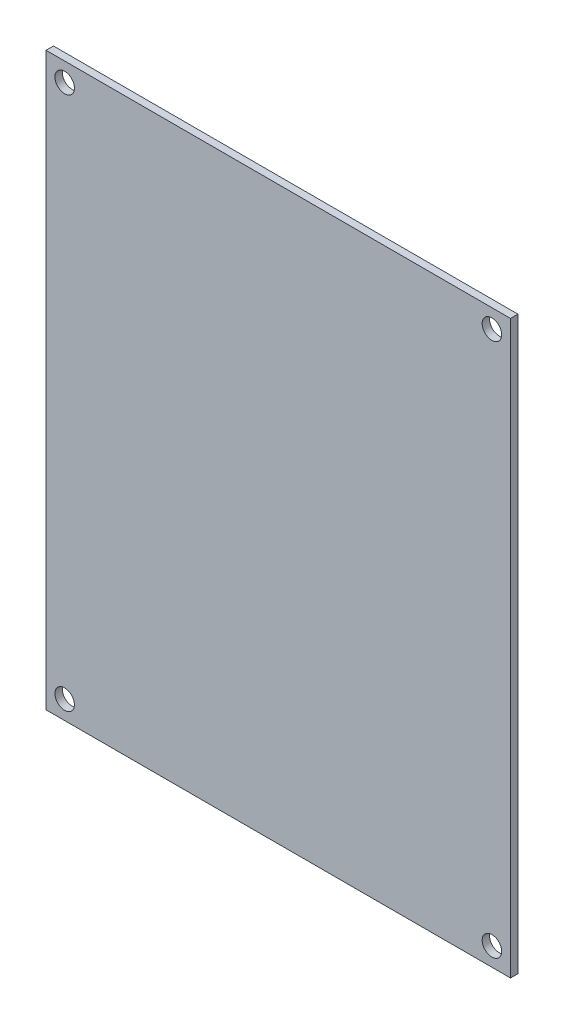
SolidWorks part; units mm, degrees
material "Custom Plastic"
ref_plane "Front Plane" through (0, 0, 0) normal (0, 0, 1) x (1, 0, 0)
ref_plane "Top Plane" through (0, 0, 0) normal (0, 1, 0) x (1, 0, 0)
ref_plane "Right Plane" through (0, 0, 0) normal (1, 0, 0) x (0, 0, -1)
sketch "Model" plane through (0, 0, 0) normal (0, 0, 1) x (1, 0, 0)
  line L0 (104.1673, 32.1811) -> (4.1672, 32.1811)
  line L1 (104.1673, 155.1806) -> (104.1673, 32.1811)
  line L2 (4.1672, 155.1806) -> (104.1673, 155.1806)
  line L3 (4.1672, 32.1811) -> (4.1672, 155.1806)
  line L4 (44.9158, 146.4259) -> (47.4224, 146.4259)
  line L5 (47.4224, 146.4259) -> (47.4224, 148.9326)
  line L6 (47.4224, 148.9326) -> (44.9158, 148.9326)
  line L7 (44.9158, 148.9326) -> (44.9158, 146.4259)
  line L8 (77.4127, 147.4278) -> (79.9193, 147.4278)
  line L9 (79.9193, 147.4278) -> (79.9193, 149.9344)
  line L10 (79.9193, 149.9344) -> (77.4127, 149.9344)
  line L11 (77.4127, 149.9344) -> (77.4127, 147.4278)
  line L12 (6.3266, 141.9721) -> (8.3592, 141.9721)
  line L13 (8.3592, 141.9721) -> (8.3592, 144.0047)
  line L14 (8.3592, 144.0047) -> (6.3266, 144.0047)
  line L15 (6.3266, 144.0047) -> (6.3266, 141.9721)
  line L16 (6.3266, 121.6529) -> (8.3592, 121.6529)
  line L17 (8.3592, 121.6529) -> (8.3592, 123.6855)
  line L18 (8.3592, 123.6855) -> (6.3266, 123.6855)
  line L19 (6.3266, 123.6855) -> (6.3266, 121.6529)
  line L20 (6.3266, 101.3324) -> (8.3592, 101.3324)
  line L21 (8.3592, 101.3324) -> (8.3592, 103.365)
  line L22 (8.3592, 103.365) -> (6.3266, 103.365)
  line L23 (6.3266, 103.365) -> (6.3266, 101.3324)
  line L24 (6.3266, 81.0118) -> (8.3592, 81.0118)
  line L25 (8.3592, 81.0118) -> (8.3592, 83.0444)
  line L26 (8.3592, 83.0444) -> (6.3266, 83.0444)
  line L27 (6.3266, 83.0444) -> (6.3266, 81.0118)
  line L28 (6.3266, 60.6927) -> (8.3592, 60.6927)
  line L29 (8.3592, 60.6927) -> (8.3592, 62.7253)
  line L30 (8.3592, 62.7253) -> (6.3266, 62.7253)
  line L31 (6.3266, 62.7253) -> (6.3266, 60.6927)
  line L32 (85.9221, 148.4144) -> (87.9547, 148.4144)
  line L33 (87.9547, 148.4144) -> (87.9547, 150.447)
  line L34 (87.9547, 150.447) -> (85.9221, 150.447)
  line L35 (85.9221, 150.447) -> (85.9221, 148.4144)
  line L36 (6.3266, 50.5324) -> (8.3592, 50.5324)
  line L37 (8.3592, 50.5324) -> (8.3592, 52.565)
  line L38 (8.3592, 52.565) -> (6.3266, 52.565)
  line L39 (6.3266, 52.565) -> (6.3266, 50.5324)
  line L40 (6.3266, 42.9118) -> (8.3592, 42.9118)
  line L41 (8.3592, 42.9118) -> (8.3592, 44.9444)
  line L42 (8.3592, 44.9444) -> (6.3266, 44.9444)
  line L43 (6.3266, 44.9444) -> (6.3266, 42.9118)
  line L44 (52.8726, 50.0418) -> (54.3815, 50.0418)
  line L45 (54.3815, 50.0418) -> (54.3815, 51.5508)
  line L46 (54.3815, 51.5508) -> (52.8726, 51.5508)
  line L47 (52.8726, 51.5508) -> (52.8726, 50.0418)
  line L48 (58.4219, 130.1637) -> (60.4545, 130.1637)
  line L49 (60.4545, 130.1637) -> (60.4545, 132.1963)
  line L50 (60.4545, 132.1963) -> (58.4219, 132.1963)
  line L51 (58.4219, 132.1963) -> (58.4219, 130.1637)
  line L52 (97.8807, 141.1439) -> (99.9133, 141.1439)
  line L53 (99.9133, 141.1439) -> (99.9133, 143.1765)
  line L54 (99.9133, 143.1765) -> (97.8807, 143.1765)
  line L55 (97.8807, 143.1765) -> (97.8807, 141.1439)
  line L56 (48.438, 37.3046) -> (48.438, 37.0552)
  line L57 (49.9456, 37.0552) -> (49.9456, 37.3046)
  line L58 (52.8877, 37.3046) -> (52.8877, 37.0552)
  line L59 (54.3967, 37.0552) -> (54.3967, 37.3046)
  line L60 (54.3126, 34.0993) -> (54.3126, 33.8995)
  line L61 (56.7201, 33.8995) -> (56.7201, 34.0993)
  line L62 (46.1133, 34.0993) -> (46.1133, 33.8995)
  line L63 (48.5207, 33.8995) -> (48.5207, 34.0993)
  line L64 (82.9607, 49.0165) -> (84.9933, 49.0165)
  line L65 (84.9933, 49.0165) -> (84.9933, 51.0492)
  line L66 (84.9933, 51.0492) -> (82.9607, 51.0492)
  line L67 (82.9607, 51.0492) -> (82.9607, 49.0165)
  line L68 (29.8828, 70.9163) -> (31.9154, 70.9163)
  line L69 (31.9154, 70.9163) -> (31.9154, 72.9489)
  line L70 (31.9154, 72.9489) -> (29.8828, 72.9489)
  line L71 (29.8828, 72.9489) -> (29.8828, 70.9163)
  line L72 (29.8828, 68.1658) -> (31.9154, 68.1658)
  line L73 (31.9154, 68.1658) -> (31.9154, 70.1984)
  line L74 (31.9154, 70.1984) -> (29.8828, 70.1984)
  line L75 (29.8828, 70.1984) -> (29.8828, 68.1658)
  line L76 (29.8828, 108.6649) -> (31.9154, 108.6649)
  line L77 (31.9154, 108.6649) -> (31.9154, 110.6975)
  line L78 (31.9154, 110.6975) -> (29.8828, 110.6975)
  line L79 (29.8828, 110.6975) -> (29.8828, 108.6649)
  line L80 (29.8828, 111.4141) -> (31.9154, 111.4141)
  line L81 (31.9154, 111.4141) -> (31.9154, 113.4467)
  line L82 (31.9154, 113.4467) -> (29.8828, 113.4467)
  line L83 (29.8828, 113.4467) -> (29.8828, 111.4141)
  line L84 (29.8828, 91.1652) -> (31.9154, 91.1652)
  line L85 (31.9154, 91.1652) -> (31.9154, 93.1978)
  line L86 (31.9154, 93.1978) -> (29.8828, 93.1978)
  line L87 (29.8828, 93.1978) -> (29.8828, 91.1652)
  line L88 (29.8828, 88.4147) -> (31.9154, 88.4147)
  line L89 (31.9154, 88.4147) -> (31.9154, 90.4473)
  line L90 (31.9154, 90.4473) -> (29.8828, 90.4473)
  line L91 (29.8828, 90.4473) -> (29.8828, 88.4147)
  line L92 (29.8828, 128.6658) -> (31.9154, 128.6658)
  line L93 (31.9154, 128.6658) -> (31.9154, 130.6984)
  line L94 (31.9154, 130.6984) -> (29.8828, 130.6984)
  line L95 (29.8828, 130.6984) -> (29.8828, 128.6658)
  line L96 (29.8828, 131.4163) -> (31.9154, 131.4163)
  line L97 (31.9154, 131.4163) -> (31.9154, 133.4489)
  line L98 (31.9154, 133.4489) -> (29.8828, 133.4489)
  line L99 (29.8828, 133.4489) -> (29.8828, 131.4163)
  line L100 (48.1611, 135.1453) -> (50.1937, 135.1453)
  line L101 (50.1937, 135.1453) -> (50.1937, 137.1779)
  line L102 (50.1937, 137.1779) -> (48.1611, 137.1779)
  line L103 (48.1611, 137.1779) -> (48.1611, 135.1453)
  line L104 (11.4074, 121.6529) -> (13.44, 121.6529)
  line L105 (13.44, 121.6529) -> (13.44, 123.6855)
  line L106 (13.44, 123.6855) -> (11.4074, 123.6855)
  line L107 (11.4074, 123.6855) -> (11.4074, 121.6529)
  line L108 (104.1673, 32.1811) -> (4.1672, 32.1811)
  line L109 (104.1673, 155.1806) -> (104.1673, 32.1811)
  line L110 (4.1672, 155.1806) -> (104.1673, 155.1806)
  line L111 (4.1672, 32.1811) -> (4.1672, 155.1806)
  spline S0 degree 3 poles (55.1711, 147.6799) (55.1711, 149.685) (52.1643, 149.685) (52.1643, 147.6799) knots 0 0 0 0 1 1 1 1
  spline S1 degree 3 poles (52.1643, 147.6799) (52.1643, 145.6749) (55.1711, 145.6749) (55.1711, 147.6799) knots 0 0 0 0 1 1 1 1
  spline S2 degree 3 poles (75.1706, 148.6804) (75.1706, 150.6854) (72.1637, 150.6854) (72.1637, 148.6804) knots 0 0 0 0 1 1 1 1
  spline S3 degree 3 poles (72.1637, 148.6804) (72.1637, 146.6754) (75.1706, 146.6754) (75.1706, 148.6804) knots 0 0 0 0 1 1 1 1
  spline S4 degree 3 poles (8.3592, 140.448) (8.3592, 141.8026) (6.3266, 141.8026) (6.3266, 140.448) knots 0 0 0 0 1 1 1 1
  spline S5 degree 3 poles (6.3266, 140.448) (6.3266, 139.0934) (8.3592, 139.0934) (8.3592, 140.448) knots 0 0 0 0 1 1 1 1
  spline S6 degree 3 poles (8.3592, 137.9083) (8.3592, 139.2629) (6.3266, 139.2629) (6.3266, 137.9083) knots 0 0 0 0 1 1 1 1
  spline S7 degree 3 poles (6.3266, 137.9083) (6.3266, 136.5537) (8.3592, 136.5537) (8.3592, 137.9083) knots 0 0 0 0 1 1 1 1
  spline S8 degree 3 poles (8.3592, 135.3686) (8.3592, 136.7232) (6.3266, 136.7232) (6.3266, 135.3686) knots 0 0 0 0 1 1 1 1
  spline S9 degree 3 poles (6.3266, 135.3686) (6.3266, 134.0139) (8.3592, 134.0139) (8.3592, 135.3686) knots 0 0 0 0 1 1 1 1
  spline S10 degree 3 poles (8.3592, 132.8288) (8.3592, 134.1834) (6.3266, 134.1834) (6.3266, 132.8288) knots 0 0 0 0 1 1 1 1
  spline S11 degree 3 poles (6.3266, 132.8288) (6.3266, 131.4742) (8.3592, 131.4742) (8.3592, 132.8288) knots 0 0 0 0 1 1 1 1
  spline S12 degree 3 poles (8.3592, 130.2891) (8.3592, 131.6437) (6.3266, 131.6437) (6.3266, 130.2891) knots 0 0 0 0 1 1 1 1
  spline S13 degree 3 poles (6.3266, 130.2891) (6.3266, 128.9331) (8.3592, 128.9331) (8.3592, 130.2891) knots 0 0 0 0 1 1 1 1
  spline S14 degree 3 poles (8.3592, 127.748) (8.3592, 129.1026) (6.3266, 129.1026) (6.3266, 127.748) knots 0 0 0 0 1 1 1 1
  spline S15 degree 3 poles (6.3266, 127.748) (6.3266, 126.3934) (8.3592, 126.3934) (8.3592, 127.748) knots 0 0 0 0 1 1 1 1
  spline S16 degree 3 poles (8.3592, 120.1288) (8.3592, 121.4834) (6.3266, 121.4834) (6.3266, 120.1288) knots 0 0 0 0 1 1 1 1
  spline S17 degree 3 poles (6.3266, 120.1288) (6.3266, 118.7742) (8.3592, 118.7742) (8.3592, 120.1288) knots 0 0 0 0 1 1 1 1
  spline S18 degree 3 poles (8.3592, 117.5891) (8.3592, 118.9437) (6.3266, 118.9437) (6.3266, 117.5891) knots 0 0 0 0 1 1 1 1
  spline S19 degree 3 poles (6.3266, 117.5891) (6.3266, 116.2331) (8.3592, 116.2331) (8.3592, 117.5891) knots 0 0 0 0 1 1 1 1
  spline S20 degree 3 poles (8.3592, 115.048) (8.3592, 116.4026) (6.3266, 116.4026) (6.3266, 115.048) knots 0 0 0 0 1 1 1 1
  spline S21 degree 3 poles (6.3266, 115.048) (6.3266, 113.6934) (8.3592, 113.6934) (8.3592, 115.048) knots 0 0 0 0 1 1 1 1
  spline S22 degree 3 poles (8.3592, 112.5083) (8.3592, 113.8629) (6.3266, 113.8629) (6.3266, 112.5083) knots 0 0 0 0 1 1 1 1
  spline S23 degree 3 poles (6.3266, 112.5083) (6.3266, 111.1537) (8.3592, 111.1537) (8.3592, 112.5083) knots 0 0 0 0 1 1 1 1
  spline S24 degree 3 poles (8.3592, 109.9686) (8.3592, 111.3232) (6.3266, 111.3232) (6.3266, 109.9686) knots 0 0 0 0 1 1 1 1
  spline S25 degree 3 poles (6.3266, 109.9686) (6.3266, 108.6139) (8.3592, 108.6139) (8.3592, 109.9686) knots 0 0 0 0 1 1 1 1
  spline S26 degree 3 poles (8.3592, 107.4288) (8.3592, 108.7834) (6.3266, 108.7834) (6.3266, 107.4288) knots 0 0 0 0 1 1 1 1
  spline S27 degree 3 poles (6.3266, 107.4288) (6.3266, 106.0742) (8.3592, 106.0742) (8.3592, 107.4288) knots 0 0 0 0 1 1 1 1
  spline S28 degree 3 poles (8.3592, 99.8083) (8.3592, 101.1629) (6.3266, 101.1629) (6.3266, 99.8083) knots 0 0 0 0 1 1 1 1
  spline S29 degree 3 poles (6.3266, 99.8083) (6.3266, 98.4537) (8.3592, 98.4537) (8.3592, 99.8083) knots 0 0 0 0 1 1 1 1
  spline S30 degree 3 poles (8.3592, 97.2686) (8.3592, 98.6232) (6.3266, 98.6232) (6.3266, 97.2686) knots 0 0 0 0 1 1 1 1
  spline S31 degree 3 poles (6.3266, 97.2686) (6.3266, 95.9139) (8.3592, 95.9139) (8.3592, 97.2686) knots 0 0 0 0 1 1 1 1
  spline S32 degree 3 poles (8.3592, 94.7288) (8.3592, 96.0834) (6.3266, 96.0834) (6.3266, 94.7288) knots 0 0 0 0 1 1 1 1
  spline S33 degree 3 poles (6.3266, 94.7288) (6.3266, 93.3742) (8.3592, 93.3742) (8.3592, 94.7288) knots 0 0 0 0 1 1 1 1
  spline S34 degree 3 poles (8.3592, 92.1891) (8.3592, 93.5437) (6.3266, 93.5437) (6.3266, 92.1891) knots 0 0 0 0 1 1 1 1
  spline S35 degree 3 poles (6.3266, 92.1891) (6.3266, 90.8331) (8.3592, 90.8331) (8.3592, 92.1891) knots 0 0 0 0 1 1 1 1
  spline S36 degree 3 poles (8.3592, 89.648) (8.3592, 91.0026) (6.3266, 91.0026) (6.3266, 89.648) knots 0 0 0 0 1 1 1 1
  spline S37 degree 3 poles (6.3266, 89.648) (6.3266, 88.2934) (8.3592, 88.2934) (8.3592, 89.648) knots 0 0 0 0 1 1 1 1
  spline S38 degree 3 poles (8.3592, 87.1083) (8.3592, 88.4629) (6.3266, 88.4629) (6.3266, 87.1083) knots 0 0 0 0 1 1 1 1
  spline S39 degree 3 poles (6.3266, 87.1083) (6.3266, 85.7537) (8.3592, 85.7537) (8.3592, 87.1083) knots 0 0 0 0 1 1 1 1
  spline S40 degree 3 poles (8.3592, 79.4891) (8.3592, 80.8437) (6.3266, 80.8437) (6.3266, 79.4891) knots 0 0 0 0 1 1 1 1
  spline S41 degree 3 poles (6.3266, 79.4891) (6.3266, 78.1331) (8.3592, 78.1331) (8.3592, 79.4891) knots 0 0 0 0 1 1 1 1
  spline S42 degree 3 poles (8.3592, 76.948) (8.3592, 78.3026) (6.3266, 78.3026) (6.3266, 76.948) knots 0 0 0 0 1 1 1 1
  spline S43 degree 3 poles (6.3266, 76.948) (6.3266, 75.5934) (8.3592, 75.5934) (8.3592, 76.948) knots 0 0 0 0 1 1 1 1
  spline S44 degree 3 poles (8.3592, 74.4083) (8.3592, 75.7629) (6.3266, 75.7629) (6.3266, 74.4083) knots 0 0 0 0 1 1 1 1
  spline S45 degree 3 poles (6.3266, 74.4083) (6.3266, 73.0537) (8.3592, 73.0537) (8.3592, 74.4083) knots 0 0 0 0 1 1 1 1
  spline S46 degree 3 poles (8.3592, 71.8685) (8.3592, 73.2232) (6.3266, 73.2232) (6.3266, 71.8685) knots 0 0 0 0 1 1 1 1
  spline S47 degree 3 poles (6.3266, 71.8685) (6.3266, 70.5139) (8.3592, 70.5139) (8.3592, 71.8685) knots 0 0 0 0 1 1 1 1
  spline S48 degree 3 poles (8.3592, 69.3288) (8.3592, 70.6834) (6.3266, 70.6834) (6.3266, 69.3288) knots 0 0 0 0 1 1 1 1
  spline S49 degree 3 poles (6.3266, 69.3288) (6.3266, 67.9742) (8.3592, 67.9742) (8.3592, 69.3288) knots 0 0 0 0 1 1 1 1
  spline S50 degree 3 poles (8.3592, 66.7891) (8.3592, 68.1437) (6.3266, 68.1437) (6.3266, 66.7891) knots 0 0 0 0 1 1 1 1
  spline S51 degree 3 poles (6.3266, 66.7891) (6.3266, 65.4331) (8.3592, 65.4331) (8.3592, 66.7891) knots 0 0 0 0 1 1 1 1
  spline S52 degree 3 poles (8.3592, 59.1686) (8.3592, 60.5232) (6.3266, 60.5232) (6.3266, 59.1686) knots 0 0 0 0 1 1 1 1
  spline S53 degree 3 poles (6.3266, 59.1686) (6.3266, 57.8139) (8.3592, 57.8139) (8.3592, 59.1686) knots 0 0 0 0 1 1 1 1
  spline S54 degree 3 poles (8.3592, 56.6288) (8.3592, 57.9834) (6.3266, 57.9834) (6.3266, 56.6288) knots 0 0 0 0 1 1 1 1
  spline S55 degree 3 poles (6.3266, 56.6288) (6.3266, 55.2742) (8.3592, 55.2742) (8.3592, 56.6288) knots 0 0 0 0 1 1 1 1
  spline S56 degree 3 poles (8.3592, 54.0891) (8.3592, 55.4437) (6.3266, 55.4437) (6.3266, 54.0891) knots 0 0 0 0 1 1 1 1
  spline S57 degree 3 poles (6.3266, 54.0891) (6.3266, 52.7331) (8.3592, 52.7331) (8.3592, 54.0891) knots 0 0 0 0 1 1 1 1
  spline S58 degree 3 poles (85.4149, 149.4301) (85.4149, 150.7847) (83.3823, 150.7847) (83.3823, 149.4301) knots 0 0 0 0 1 1 1 1
  spline S59 degree 3 poles (83.3823, 149.4301) (83.3823, 148.0754) (85.4149, 148.0754) (85.4149, 149.4301) knots 0 0 0 0 1 1 1 1
  spline S60 degree 3 poles (8.3592, 49.0083) (8.3592, 50.3629) (6.3266, 50.3629) (6.3266, 49.0083) knots 0 0 0 0 1 1 1 1
  spline S61 degree 3 poles (6.3266, 49.0083) (6.3266, 47.6537) (8.3592, 47.6537) (8.3592, 49.0083) knots 0 0 0 0 1 1 1 1
  spline S62 degree 3 poles (8.3592, 41.3891) (8.3592, 42.7437) (6.3266, 42.7437) (6.3266, 41.3891) knots 0 0 0 0 1 1 1 1
  spline S63 degree 3 poles (6.3266, 41.3891) (6.3266, 40.0331) (8.3592, 40.0331) (8.3592, 41.3891) knots 0 0 0 0 1 1 1 1
  spline S64 degree 3 poles (54.3815, 52.0661) (54.3815, 53.0721) (52.8726, 53.0721) (52.8726, 52.0661) knots 0 0 0 0 1 1 1 1
  spline S65 degree 3 poles (52.8726, 52.0661) (52.8726, 51.0602) (54.3815, 51.0602) (54.3815, 52.0661) knots 0 0 0 0 1 1 1 1
  spline S66 degree 3 poles (55.6507, 50.797) (55.6507, 51.8029) (54.1417, 51.8029) (54.1417, 50.797) knots 0 0 0 0 1 1 1 1
  spline S67 degree 3 poles (54.1417, 50.797) (54.1417, 49.791) (55.6507, 49.791) (55.6507, 50.797) knots 0 0 0 0 1 1 1 1
  spline S68 degree 3 poles (55.6507, 52.0661) (55.6507, 53.0721) (54.1417, 53.0721) (54.1417, 52.0661) knots 0 0 0 0 1 1 1 1
  spline S69 degree 3 poles (54.1417, 52.0661) (54.1417, 51.0602) (55.6507, 51.0602) (55.6507, 52.0661) knots 0 0 0 0 1 1 1 1
  spline S70 degree 3 poles (56.9212, 50.797) (56.9212, 51.8029) (55.4123, 51.8029) (55.4123, 50.797) knots 0 0 0 0 1 1 1 1
  spline S71 degree 3 poles (55.4123, 50.797) (55.4123, 49.791) (56.9212, 49.791) (56.9212, 50.797) knots 0 0 0 0 1 1 1 1
  spline S72 degree 3 poles (56.9212, 52.0661) (56.9212, 53.0721) (55.4123, 53.0721) (55.4123, 52.0661) knots 0 0 0 0 1 1 1 1
  spline S73 degree 3 poles (55.4123, 52.0661) (55.4123, 51.0602) (56.9212, 51.0602) (56.9212, 52.0661) knots 0 0 0 0 1 1 1 1
  spline S74 degree 3 poles (58.1904, 50.797) (58.1904, 51.8029) (56.6828, 51.8029) (56.6828, 50.797) knots 0 0 0 0 1 1 1 1
  spline S75 degree 3 poles (56.6828, 50.797) (56.6828, 49.791) (58.1904, 49.791) (58.1904, 50.797) knots 0 0 0 0 1 1 1 1
  spline S76 degree 3 poles (58.1904, 52.0661) (58.1904, 53.0721) (56.6828, 53.0721) (56.6828, 52.0661) knots 0 0 0 0 1 1 1 1
  spline S77 degree 3 poles (56.6828, 52.0661) (56.6828, 51.0602) (58.1904, 51.0602) (58.1904, 52.0661) knots 0 0 0 0 1 1 1 1
  spline S78 degree 3 poles (59.461, 50.797) (59.461, 51.8029) (57.952, 51.8029) (57.952, 50.797) knots 0 0 0 0 1 1 1 1
  spline S79 degree 3 poles (57.952, 50.797) (57.952, 49.791) (59.461, 49.791) (59.461, 50.797) knots 0 0 0 0 1 1 1 1
  spline S80 degree 3 poles (59.461, 52.0661) (59.461, 53.0721) (57.952, 53.0721) (57.952, 52.0661) knots 0 0 0 0 1 1 1 1
  spline S81 degree 3 poles (57.952, 52.0661) (57.952, 51.0602) (59.461, 51.0602) (59.461, 52.0661) knots 0 0 0 0 1 1 1 1
  spline S82 degree 3 poles (57.9148, 131.1793) (57.9148, 132.5353) (55.8822, 132.5353) (55.8822, 131.1793) knots 0 0 0 0 1 1 1 1
  spline S83 degree 3 poles (55.8822, 131.1793) (55.8822, 129.8247) (57.9148, 129.8247) (57.9148, 131.1793) knots 0 0 0 0 1 1 1 1
  spline S84 degree 3 poles (63.2437, 36.9311) (63.2437, 37.9371) (61.7347, 37.9371) (61.7347, 36.9311) knots 0 0 0 0 1 1 1 1
  spline S85 degree 3 poles (61.7347, 36.9311) (61.7347, 35.9252) (63.2437, 35.9252) (63.2437, 36.9311) knots 0 0 0 0 1 1 1 1
  spline S86 degree 3 poles (71.2239, 36.9311) (71.2239, 37.9371) (69.715, 37.9371) (69.715, 36.9311) knots 0 0 0 0 1 1 1 1
  spline S87 degree 3 poles (69.715, 36.9311) (69.715, 35.9252) (71.2239, 35.9252) (71.2239, 36.9311) knots 0 0 0 0 1 1 1 1
  spline S88 degree 3 poles (102.453, 142.1609) (102.453, 143.5155) (100.4204, 143.5155) (100.4204, 142.1609) knots 0 0 0 0 1 1 1 1
  spline S89 degree 3 poles (100.4204, 142.1609) (100.4204, 140.8063) (102.453, 140.8063) (102.453, 142.1609) knots 0 0 0 0 1 1 1 1
  spline S90 degree 3 poles (99.9133, 129.4609) (99.9133, 130.8155) (97.8807, 130.8155) (97.8807, 129.4609) knots 0 0 0 0 1 1 1 1
  spline S91 degree 3 poles (97.8807, 129.4609) (97.8807, 128.1063) (99.9133, 128.1063) (99.9133, 129.4609) knots 0 0 0 0 1 1 1 1
  spline S92 degree 3 poles (102.453, 139.6198) (102.453, 140.9744) (100.4204, 140.9744) (100.4204, 139.6198) knots 0 0 0 0 1 1 1 1
  spline S93 degree 3 poles (100.4204, 139.6198) (100.4204, 138.2652) (102.453, 138.2652) (102.453, 139.6198) knots 0 0 0 0 1 1 1 1
  spline S94 degree 3 poles (99.9133, 126.9198) (99.9133, 128.2744) (97.8807, 128.2744) (97.8807, 126.9198) knots 0 0 0 0 1 1 1 1
  spline S95 degree 3 poles (97.8807, 126.9198) (97.8807, 125.5652) (99.9133, 125.5652) (99.9133, 126.9198) knots 0 0 0 0 1 1 1 1
  spline S96 degree 3 poles (102.453, 137.0801) (102.453, 138.4347) (100.4204, 138.4347) (100.4204, 137.0801) knots 0 0 0 0 1 1 1 1
  spline S97 degree 3 poles (100.4204, 137.0801) (100.4204, 135.7255) (102.453, 135.7255) (102.453, 137.0801) knots 0 0 0 0 1 1 1 1
  spline S98 degree 3 poles (99.9133, 124.3801) (99.9133, 125.7347) (97.8807, 125.7347) (97.8807, 124.3801) knots 0 0 0 0 1 1 1 1
  spline S99 degree 3 poles (97.8807, 124.3801) (97.8807, 123.0255) (99.9133, 123.0255) (99.9133, 124.3801) knots 0 0 0 0 1 1 1 1
  spline S100 degree 3 poles (102.453, 134.5403) (102.453, 135.895) (100.4204, 135.895) (100.4204, 134.5403) knots 0 0 0 0 1 1 1 1
  spline S101 degree 3 poles (100.4204, 134.5403) (100.4204, 133.1857) (102.453, 133.1857) (102.453, 134.5403) knots 0 0 0 0 1 1 1 1
  spline S102 degree 3 poles (99.9133, 121.8404) (99.9133, 123.195) (97.8807, 123.195) (97.8807, 121.8404) knots 0 0 0 0 1 1 1 1
  spline S103 degree 3 poles (97.8807, 121.8404) (97.8807, 120.4857) (99.9133, 120.4857) (99.9133, 121.8404) knots 0 0 0 0 1 1 1 1
  spline S104 degree 3 poles (102.453, 132.0006) (102.453, 133.3552) (100.4204, 133.3552) (100.4204, 132.0006) knots 0 0 0 0 1 1 1 1
  spline S105 degree 3 poles (100.4204, 132.0006) (100.4204, 130.646) (102.453, 130.646) (102.453, 132.0006) knots 0 0 0 0 1 1 1 1
  spline S106 degree 3 poles (99.9133, 119.3006) (99.9133, 120.6552) (97.8807, 120.6552) (97.8807, 119.3006) knots 0 0 0 0 1 1 1 1
  spline S107 degree 3 poles (97.8807, 119.3006) (97.8807, 117.946) (99.9133, 117.946) (99.9133, 119.3006) knots 0 0 0 0 1 1 1 1
  spline S108 degree 3 poles (102.453, 129.4609) (102.453, 130.8155) (100.4204, 130.8155) (100.4204, 129.4609) knots 0 0 0 0 1 1 1 1
  spline S109 degree 3 poles (100.4204, 129.4609) (100.4204, 128.1063) (102.453, 128.1063) (102.453, 129.4609) knots 0 0 0 0 1 1 1 1
  spline S110 degree 3 poles (99.9133, 116.7609) (99.9133, 118.1155) (97.8807, 118.1155) (97.8807, 116.7609) knots 0 0 0 0 1 1 1 1
  spline S111 degree 3 poles (97.8807, 116.7609) (97.8807, 115.4063) (99.9133, 115.4063) (99.9133, 116.7609) knots 0 0 0 0 1 1 1 1
  spline S112 degree 3 poles (102.453, 126.9198) (102.453, 128.2744) (100.4204, 128.2744) (100.4204, 126.9198) knots 0 0 0 0 1 1 1 1
  spline S113 degree 3 poles (100.4204, 126.9198) (100.4204, 125.5652) (102.453, 125.5652) (102.453, 126.9198) knots 0 0 0 0 1 1 1 1
  spline S114 degree 3 poles (99.9133, 114.2198) (99.9133, 115.5744) (97.8807, 115.5744) (97.8807, 114.2198) knots 0 0 0 0 1 1 1 1
  spline S115 degree 3 poles (97.8807, 114.2198) (97.8807, 112.8652) (99.9133, 112.8652) (99.9133, 114.2198) knots 0 0 0 0 1 1 1 1
  spline S116 degree 3 poles (102.453, 124.3801) (102.453, 125.7347) (100.4204, 125.7347) (100.4204, 124.3801) knots 0 0 0 0 1 1 1 1
  spline S117 degree 3 poles (100.4204, 124.3801) (100.4204, 123.0255) (102.453, 123.0255) (102.453, 124.3801) knots 0 0 0 0 1 1 1 1
  spline S118 degree 3 poles (99.9133, 111.6801) (99.9133, 113.0347) (97.8807, 113.0347) (97.8807, 111.6801) knots 0 0 0 0 1 1 1 1
  spline S119 degree 3 poles (97.8807, 111.6801) (97.8807, 110.3255) (99.9133, 110.3255) (99.9133, 111.6801) knots 0 0 0 0 1 1 1 1
  spline S120 degree 3 poles (102.453, 121.8404) (102.453, 123.195) (100.4204, 123.195) (100.4204, 121.8404) knots 0 0 0 0 1 1 1 1
  spline S121 degree 3 poles (100.4204, 121.8404) (100.4204, 120.4857) (102.453, 120.4857) (102.453, 121.8404) knots 0 0 0 0 1 1 1 1
  spline S122 degree 3 poles (99.9133, 109.1404) (99.9133, 110.495) (97.8807, 110.495) (97.8807, 109.1404) knots 0 0 0 0 1 1 1 1
  spline S123 degree 3 poles (97.8807, 109.1404) (97.8807, 107.7857) (99.9133, 107.7857) (99.9133, 109.1404) knots 0 0 0 0 1 1 1 1
  spline S124 degree 3 poles (102.453, 119.3006) (102.453, 120.6552) (100.4204, 120.6552) (100.4204, 119.3006) knots 0 0 0 0 1 1 1 1
  spline S125 degree 3 poles (100.4204, 119.3006) (100.4204, 117.946) (102.453, 117.946) (102.453, 119.3006) knots 0 0 0 0 1 1 1 1
  spline S126 degree 3 poles (99.9133, 106.6006) (99.9133, 107.9552) (97.8807, 107.9552) (97.8807, 106.6006) knots 0 0 0 0 1 1 1 1
  spline S127 degree 3 poles (97.8807, 106.6006) (97.8807, 105.246) (99.9133, 105.246) (99.9133, 106.6006) knots 0 0 0 0 1 1 1 1
  spline S128 degree 3 poles (102.453, 116.7609) (102.453, 118.1155) (100.4204, 118.1155) (100.4204, 116.7609) knots 0 0 0 0 1 1 1 1
  spline S129 degree 3 poles (100.4204, 116.7609) (100.4204, 115.4063) (102.453, 115.4063) (102.453, 116.7609) knots 0 0 0 0 1 1 1 1
  spline S130 degree 3 poles (99.9133, 104.0609) (99.9133, 105.4155) (97.8807, 105.4155) (97.8807, 104.0609) knots 0 0 0 0 1 1 1 1
  spline S131 degree 3 poles (97.8807, 104.0609) (97.8807, 102.7063) (99.9133, 102.7063) (99.9133, 104.0609) knots 0 0 0 0 1 1 1 1
  spline S132 degree 3 poles (102.453, 114.2198) (102.453, 115.5744) (100.4204, 115.5744) (100.4204, 114.2198) knots 0 0 0 0 1 1 1 1
  spline S133 degree 3 poles (100.4204, 114.2198) (100.4204, 112.8652) (102.453, 112.8652) (102.453, 114.2198) knots 0 0 0 0 1 1 1 1
  spline S134 degree 3 poles (102.453, 111.6801) (102.453, 113.0347) (100.4204, 113.0347) (100.4204, 111.6801) knots 0 0 0 0 1 1 1 1
  spline S135 degree 3 poles (100.4204, 111.6801) (100.4204, 110.3255) (102.453, 110.3255) (102.453, 111.6801) knots 0 0 0 0 1 1 1 1
  spline S136 degree 3 poles (99.9133, 101.5198) (99.9133, 102.8744) (97.8807, 102.8744) (97.8807, 101.5198) knots 0 0 0 0 1 1 1 1
  spline S137 degree 3 poles (97.8807, 101.5198) (97.8807, 100.1652) (99.9133, 100.1652) (99.9133, 101.5198) knots 0 0 0 0 1 1 1 1
  spline S138 degree 3 poles (102.453, 109.1404) (102.453, 110.495) (100.4204, 110.495) (100.4204, 109.1404) knots 0 0 0 0 1 1 1 1
  spline S139 degree 3 poles (100.4204, 109.1404) (100.4204, 107.7857) (102.453, 107.7857) (102.453, 109.1404) knots 0 0 0 0 1 1 1 1
  spline S140 degree 3 poles (102.453, 104.0609) (102.453, 105.4155) (100.4204, 105.4155) (100.4204, 104.0609) knots 0 0 0 0 1 1 1 1
  spline S141 degree 3 poles (100.4204, 104.0609) (100.4204, 102.7063) (102.453, 102.7063) (102.453, 104.0609) knots 0 0 0 0 1 1 1 1
  spline S142 degree 3 poles (102.453, 101.5198) (102.453, 102.8744) (100.4204, 102.8744) (100.4204, 101.5198) knots 0 0 0 0 1 1 1 1
  spline S143 degree 3 poles (100.4204, 101.5198) (100.4204, 100.1652) (102.453, 100.1652) (102.453, 101.5198) knots 0 0 0 0 1 1 1 1
  spline S144 degree 3 poles (102.453, 98.9801) (102.453, 100.3347) (100.4204, 100.3347) (100.4204, 98.9801) knots 0 0 0 0 1 1 1 1
  spline S145 degree 3 poles (100.4204, 98.9801) (100.4204, 97.6255) (102.453, 97.6255) (102.453, 98.9801) knots 0 0 0 0 1 1 1 1
  spline S146 degree 3 poles (102.453, 96.4404) (102.453, 97.795) (100.4204, 97.795) (100.4204, 96.4404) knots 0 0 0 0 1 1 1 1
  spline S147 degree 3 poles (100.4204, 96.4404) (100.4204, 95.0857) (102.453, 95.0857) (102.453, 96.4404) knots 0 0 0 0 1 1 1 1
  spline S148 degree 3 poles (99.9133, 98.9801) (99.9133, 100.3347) (97.8807, 100.3347) (97.8807, 98.9801) knots 0 0 0 0 1 1 1 1
  spline S149 degree 3 poles (97.8807, 98.9801) (97.8807, 97.6255) (99.9133, 97.6255) (99.9133, 98.9801) knots 0 0 0 0 1 1 1 1
  spline S150 degree 3 poles (99.9133, 96.4404) (99.9133, 97.795) (97.8807, 97.795) (97.8807, 96.4404) knots 0 0 0 0 1 1 1 1
  spline S151 degree 3 poles (97.8807, 96.4404) (97.8807, 95.0857) (99.9133, 95.0857) (99.9133, 96.4404) knots 0 0 0 0 1 1 1 1
  spline S152 degree 3 poles (99.9133, 139.6198) (99.9133, 140.9744) (97.8807, 140.9744) (97.8807, 139.6198) knots 0 0 0 0 1 1 1 1
  spline S153 degree 3 poles (97.8807, 139.6198) (97.8807, 138.2652) (99.9133, 138.2652) (99.9133, 139.6198) knots 0 0 0 0 1 1 1 1
  spline S154 degree 3 poles (99.9133, 137.0801) (99.9133, 138.4347) (97.8807, 138.4347) (97.8807, 137.0801) knots 0 0 0 0 1 1 1 1
  spline S155 degree 3 poles (97.8807, 137.0801) (97.8807, 135.7255) (99.9133, 135.7255) (99.9133, 137.0801) knots 0 0 0 0 1 1 1 1
  spline S156 degree 3 poles (99.9133, 134.5403) (99.9133, 135.895) (97.8807, 135.895) (97.8807, 134.5403) knots 0 0 0 0 1 1 1 1
  spline S157 degree 3 poles (97.8807, 134.5403) (97.8807, 133.1857) (99.9133, 133.1857) (99.9133, 134.5403) knots 0 0 0 0 1 1 1 1
  spline S158 degree 3 poles (99.9133, 132.0006) (99.9133, 133.3552) (97.8807, 133.3552) (97.8807, 132.0006) knots 0 0 0 0 1 1 1 1
  spline S159 degree 3 poles (97.8807, 132.0006) (97.8807, 130.646) (99.9133, 130.646) (99.9133, 132.0006) knots 0 0 0 0 1 1 1 1
  spline S160 degree 3 poles (99.9133, 93.9006) (99.9133, 95.2552) (97.8807, 95.2552) (97.8807, 93.9006) knots 0 0 0 0 1 1 1 1
  spline S161 degree 3 poles (97.8807, 93.9006) (97.8807, 92.546) (99.9133, 92.546) (99.9133, 93.9006) knots 0 0 0 0 1 1 1 1
  spline S162 degree 3 poles (102.453, 93.9006) (102.453, 95.2552) (100.4204, 95.2552) (100.4204, 93.9006) knots 0 0 0 0 1 1 1 1
  spline S163 degree 3 poles (100.4204, 93.9006) (100.4204, 92.546) (102.453, 92.546) (102.453, 93.9006) knots 0 0 0 0 1 1 1 1
  spline S164 degree 3 poles (102.453, 106.6006) (102.453, 107.9552) (100.4204, 107.9552) (100.4204, 106.6006) knots 0 0 0 0 1 1 1 1
  spline S165 degree 3 poles (100.4204, 106.6006) (100.4204, 105.246) (102.453, 105.246) (102.453, 106.6006) knots 0 0 0 0 1 1 1 1
  spline S166 degree 3 poles (99.9133, 91.3609) (99.9133, 92.7155) (97.8807, 92.7155) (97.8807, 91.3609) knots 0 0 0 0 1 1 1 1
  spline S167 degree 3 poles (97.8807, 91.3609) (97.8807, 90.0063) (99.9133, 90.0063) (99.9133, 91.3609) knots 0 0 0 0 1 1 1 1
  spline S168 degree 3 poles (102.453, 91.3609) (102.453, 92.7155) (100.4204, 92.7155) (100.4204, 91.3609) knots 0 0 0 0 1 1 1 1
  spline S169 degree 3 poles (100.4204, 91.3609) (100.4204, 90.0063) (102.453, 90.0063) (102.453, 91.3609) knots 0 0 0 0 1 1 1 1
  spline S170 degree 3 poles (99.9133, 88.8198) (99.9133, 90.1744) (97.8807, 90.1744) (97.8807, 88.8198) knots 0 0 0 0 1 1 1 1
  spline S171 degree 3 poles (97.8807, 88.8198) (97.8807, 87.4652) (99.9133, 87.4652) (99.9133, 88.8198) knots 0 0 0 0 1 1 1 1
  spline S172 degree 3 poles (102.453, 88.8198) (102.453, 90.1744) (100.4204, 90.1744) (100.4204, 88.8198) knots 0 0 0 0 1 1 1 1
  spline S173 degree 3 poles (100.4204, 88.8198) (100.4204, 87.4652) (102.453, 87.4652) (102.453, 88.8198) knots 0 0 0 0 1 1 1 1
  spline S174 degree 3 poles (99.9133, 86.2801) (99.9133, 87.6347) (97.8807, 87.6347) (97.8807, 86.2801) knots 0 0 0 0 1 1 1 1
  spline S175 degree 3 poles (97.8807, 86.2801) (97.8807, 84.9255) (99.9133, 84.9255) (99.9133, 86.2801) knots 0 0 0 0 1 1 1 1
  spline S176 degree 3 poles (102.453, 86.2801) (102.453, 87.6347) (100.4204, 87.6347) (100.4204, 86.2801) knots 0 0 0 0 1 1 1 1
  spline S177 degree 3 poles (100.4204, 86.2801) (100.4204, 84.9255) (102.453, 84.9255) (102.453, 86.2801) knots 0 0 0 0 1 1 1 1
  spline S178 degree 3 poles (99.9133, 83.7404) (99.9133, 85.095) (97.8807, 85.095) (97.8807, 83.7404) knots 0 0 0 0 1 1 1 1
  spline S179 degree 3 poles (97.8807, 83.7404) (97.8807, 82.3857) (99.9133, 82.3857) (99.9133, 83.7404) knots 0 0 0 0 1 1 1 1
  spline S180 degree 3 poles (102.453, 83.7404) (102.453, 85.095) (100.4204, 85.095) (100.4204, 83.7404) knots 0 0 0 0 1 1 1 1
  spline S181 degree 3 poles (100.4204, 83.7404) (100.4204, 82.3857) (102.453, 82.3857) (102.453, 83.7404) knots 0 0 0 0 1 1 1 1
  spline S182 degree 3 poles (99.9133, 81.2006) (99.9133, 82.5552) (97.8807, 82.5552) (97.8807, 81.2006) knots 0 0 0 0 1 1 1 1
  spline S183 degree 3 poles (97.8807, 81.2006) (97.8807, 79.846) (99.9133, 79.846) (99.9133, 81.2006) knots 0 0 0 0 1 1 1 1
  spline S184 degree 3 poles (102.453, 81.2006) (102.453, 82.5552) (100.4204, 82.5552) (100.4204, 81.2006) knots 0 0 0 0 1 1 1 1
  spline S185 degree 3 poles (100.4204, 81.2006) (100.4204, 79.846) (102.453, 79.846) (102.453, 81.2006) knots 0 0 0 0 1 1 1 1
  spline S186 degree 3 poles (49.9456, 37.3046) (49.9456, 38.3106) (48.438, 38.3106) (48.438, 37.3046) knots 0 0 0 0 1 1 1 1
  spline S187 degree 3 poles (48.438, 37.0552) (48.438, 36.0492) (49.9456, 36.0492) (49.9456, 37.0552) knots 0 0 0 0 1 1 1 1
  spline S188 degree 3 poles (54.3967, 37.3046) (54.3967, 38.3106) (52.8877, 38.3106) (52.8877, 37.3046) knots 0 0 0 0 1 1 1 1
  spline S189 degree 3 poles (52.8877, 37.0552) (52.8877, 36.0492) (54.3967, 36.0492) (54.3967, 37.0552) knots 0 0 0 0 1 1 1 1
  spline S190 degree 3 poles (56.7201, 34.0993) (56.7201, 35.7047) (54.3126, 35.7047) (54.3126, 34.0993) knots 0 0 0 0 1 1 1 1
  spline S191 degree 3 poles (54.3126, 33.8995) (54.3126, 32.2941) (56.7201, 32.2941) (56.7201, 33.8995) knots 0 0 0 0 1 1 1 1
  spline S192 degree 3 poles (48.5207, 34.0993) (48.5207, 35.7047) (46.1133, 35.7047) (46.1133, 34.0993) knots 0 0 0 0 1 1 1 1
  spline S193 degree 3 poles (46.1133, 33.8995) (46.1133, 32.2941) (48.5207, 32.2941) (48.5207, 33.8995) knots 0 0 0 0 1 1 1 1
  spline S194 degree 3 poles (54.4711, 34.0001) (54.4711, 34.9054) (53.1123, 34.9054) (53.1123, 34.0001) knots 0 0 0 0 1 1 1 1
  spline S195 degree 3 poles (53.1123, 34.0001) (53.1123, 33.0933) (54.4711, 33.0933) (54.4711, 34.0001) knots 0 0 0 0 1 1 1 1
  spline S196 degree 3 poles (49.721, 34.0001) (49.721, 34.9054) (48.3623, 34.9054) (48.3623, 34.0001) knots 0 0 0 0 1 1 1 1
  spline S197 degree 3 poles (48.3623, 34.0001) (48.3623, 33.0933) (49.721, 33.0933) (49.721, 34.0001) knots 0 0 0 0 1 1 1 1
  spline S198 degree 3 poles (84.606, 43.6822) (84.606, 46.2205) (80.7985, 46.2205) (80.7985, 43.6822) knots 0 0 0 0 1 1 1 1
  spline S199 degree 3 poles (80.7985, 43.6822) (80.7985, 41.1438) (84.606, 41.1438) (84.606, 43.6822) knots 0 0 0 0 1 1 1 1
  spline S200 degree 3 poles (96.0355, 43.6822) (96.0355, 46.2205) (92.228, 46.2205) (92.228, 43.6822) knots 0 0 0 0 1 1 1 1
  spline S201 degree 3 poles (92.228, 43.6822) (92.228, 41.1438) (96.0355, 41.1438) (96.0355, 43.6822) knots 0 0 0 0 1 1 1 1
  spline S202 degree 3 poles (93.8775, 52.5719) (93.8775, 53.9265) (91.8462, 53.9265) (91.8462, 52.5719) knots 0 0 0 0 1 1 1 1
  spline S203 degree 3 poles (91.8462, 52.5719) (91.8462, 51.2173) (93.8775, 51.2173) (93.8775, 52.5719) knots 0 0 0 0 1 1 1 1
  spline S204 degree 3 poles (92.6124, 50.0322) (92.6124, 51.3868) (90.5812, 51.3868) (90.5812, 50.0322) knots 0 0 0 0 1 1 1 1
  spline S205 degree 3 poles (90.5812, 50.0322) (90.5812, 48.6775) (92.6124, 48.6775) (92.6124, 50.0322) knots 0 0 0 0 1 1 1 1
  spline S206 degree 3 poles (91.3377, 52.5719) (91.3377, 53.9265) (89.3065, 53.9265) (89.3065, 52.5719) knots 0 0 0 0 1 1 1 1
  spline S207 degree 3 poles (89.3065, 52.5719) (89.3065, 51.2173) (91.3377, 51.2173) (91.3377, 52.5719) knots 0 0 0 0 1 1 1 1
  spline S208 degree 3 poles (90.0727, 50.0322) (90.0727, 51.3868) (88.0415, 51.3868) (88.0415, 50.0322) knots 0 0 0 0 1 1 1 1
  spline S209 degree 3 poles (88.0415, 50.0322) (88.0415, 48.6775) (90.0727, 48.6775) (90.0727, 50.0322) knots 0 0 0 0 1 1 1 1
  spline S210 degree 3 poles (88.798, 52.5719) (88.798, 53.9265) (86.7654, 53.9265) (86.7654, 52.5719) knots 0 0 0 0 1 1 1 1
  spline S211 degree 3 poles (86.7654, 52.5719) (86.7654, 51.2173) (88.798, 51.2173) (88.798, 52.5719) knots 0 0 0 0 1 1 1 1
  spline S212 degree 3 poles (87.533, 50.0322) (87.533, 51.3868) (85.5018, 51.3868) (85.5018, 50.0322) knots 0 0 0 0 1 1 1 1
  spline S213 degree 3 poles (85.5018, 50.0322) (85.5018, 48.6775) (87.533, 48.6775) (87.533, 50.0322) knots 0 0 0 0 1 1 1 1
  spline S214 degree 3 poles (86.2583, 52.5719) (86.2583, 53.9265) (84.2257, 53.9265) (84.2257, 52.5719) knots 0 0 0 0 1 1 1 1
  spline S215 degree 3 poles (84.2257, 52.5719) (84.2257, 51.2173) (86.2583, 51.2173) (86.2583, 52.5719) knots 0 0 0 0 1 1 1 1
  spline S216 degree 3 poles (82.1945, 46.7331) (82.1945, 48.7644) (79.1462, 48.7644) (79.1462, 46.7331) knots 0 0 0 0 1 1 1 1
  spline S217 degree 3 poles (79.1462, 46.7331) (79.1462, 44.7005) (82.1945, 44.7005) (82.1945, 46.7331) knots 0 0 0 0 1 1 1 1
  spline S218 degree 3 poles (97.6877, 46.7304) (97.6877, 48.7616) (94.6395, 48.7616) (94.6395, 46.7304) knots 0 0 0 0 1 1 1 1
  spline S219 degree 3 poles (94.6395, 46.7304) (94.6395, 44.6978) (97.6877, 44.6978) (97.6877, 46.7304) knots 0 0 0 0 1 1 1 1
  spline S220 degree 3 poles (93.5178, 38.7819) (93.5178, 40.1365) (91.4852, 40.1365) (91.4852, 38.7819) knots 0 0 0 0 1 1 1 1
  spline S221 degree 3 poles (91.4852, 38.7819) (91.4852, 37.4272) (93.5178, 37.4272) (93.5178, 38.7819) knots 0 0 0 0 1 1 1 1
  spline S222 degree 3 poles (85.3488, 38.7819) (85.3488, 40.1365) (83.3162, 40.1365) (83.3162, 38.7819) knots 0 0 0 0 1 1 1 1
  spline S223 degree 3 poles (83.3162, 38.7819) (83.3162, 37.4272) (85.3488, 37.4272) (85.3488, 38.7819) knots 0 0 0 0 1 1 1 1
  spline S224 degree 3 poles (96.0575, 38.7819) (96.0575, 40.1365) (94.0249, 40.1365) (94.0249, 38.7819) knots 0 0 0 0 1 1 1 1
  spline S225 degree 3 poles (94.0249, 38.7819) (94.0249, 37.4272) (96.0575, 37.4272) (96.0575, 38.7819) knots 0 0 0 0 1 1 1 1
  spline S226 degree 3 poles (82.8091, 38.7819) (82.8091, 40.1365) (80.7765, 40.1365) (80.7765, 38.7819) knots 0 0 0 0 1 1 1 1
  spline S227 degree 3 poles (80.7765, 38.7819) (80.7765, 37.4272) (82.8091, 37.4272) (82.8091, 38.7819) knots 0 0 0 0 1 1 1 1
  spline S228 degree 3 poles (102.9215, 36.1815) (102.9215, 37.7029) (101.6882, 38.9362) (100.1668, 38.9362) knots 0 0 0 0 1 1 1 1
  spline S229 degree 3 poles (100.1668, 38.9362) (98.6455, 38.9362) (97.4121, 37.7028) (97.4121, 36.1815) knots 0 0 0 0 1 1 1 1
  spline S230 degree 3 poles (97.4121, 36.1815) (97.4121, 34.6601) (98.6455, 33.4268) (100.1668, 33.4268) knots 0 0 0 0 1 1 1 1
  spline S231 degree 3 poles (100.1668, 33.4268) (101.6882, 33.4268) (102.9215, 34.6601) (102.9215, 36.1815) knots 0 0 0 0 1 1 1 1
  spline S232 degree 3 poles (10.9223, 36.1815) (10.9223, 37.7028) (9.689, 38.9362) (8.1676, 38.9362) knots 0 0 0 0 1 1 1 1
  spline S233 degree 3 poles (8.1676, 38.9362) (6.6463, 38.9362) (5.4129, 37.7028) (5.4129, 36.1815) knots 0 0 0 0 1 1 1 1
  spline S234 degree 3 poles (5.4129, 36.1815) (5.4129, 34.6601) (6.6463, 33.4268) (8.1676, 33.4268) knots 0 0 0 0 1 1 1 1
  spline S235 degree 3 poles (8.1676, 33.4268) (9.689, 33.4268) (10.9223, 34.6601) (10.9223, 36.1815) knots 0 0 0 0 1 1 1 1
  spline S236 degree 3 poles (10.9223, 151.1802) (10.9223, 152.7015) (9.689, 153.9349) (8.1676, 153.9349) knots 0 0 0 0 1 1 1 1
  spline S237 degree 3 poles (8.1676, 153.9349) (6.6463, 153.9349) (5.4129, 152.7015) (5.4129, 151.1802) knots 0 0 0 0 1 1 1 1
  spline S238 degree 3 poles (5.4129, 151.1802) (5.4129, 149.6588) (6.6463, 148.4255) (8.1676, 148.4255) knots 0 0 0 0 1 1 1 1
  spline S239 degree 3 poles (8.1676, 148.4255) (9.689, 148.4255) (10.9223, 149.6588) (10.9223, 151.1802) knots 0 0 0 0 1 1 1 1
  spline S240 degree 3 poles (102.9215, 151.1802) (102.9215, 152.7015) (101.6882, 153.9349) (100.1668, 153.9349) knots 0 0 0 0 1 1 1 1
  spline S241 degree 3 poles (100.1668, 153.9349) (98.6455, 153.9349) (97.4121, 152.7015) (97.4121, 151.1802) knots 0 0 0 0 1 1 1 1
  spline S242 degree 3 poles (97.4121, 151.1802) (97.4121, 149.6588) (98.6455, 148.4255) (100.1668, 148.4255) knots 0 0 0 0 1 1 1 1
  spline S243 degree 3 poles (100.1668, 148.4255) (101.6882, 148.4255) (102.9215, 149.6588) (102.9215, 151.1802) knots 0 0 0 0 1 1 1 1
  spline S244 degree 3 poles (44.3218, 98.681) (44.3218, 99.5533) (43.0127, 99.5533) (43.0127, 98.681) knots 0 0 0 0 1 1 1 1
  spline S245 degree 3 poles (43.0127, 98.681) (43.0127, 97.8087) (44.3218, 97.8087) (44.3218, 98.681) knots 0 0 0 0 1 1 1 1
  spline S246 degree 3 poles (43.8216, 138.9322) (43.8216, 139.8045) (42.5125, 139.8045) (42.5125, 138.9322) knots 0 0 0 0 1 1 1 1
  spline S247 degree 3 poles (42.5125, 138.9322) (42.5125, 138.0599) (43.8216, 138.0599) (43.8216, 138.9322) knots 0 0 0 0 1 1 1 1
  spline S248 degree 3 poles (44.3218, 119.1807) (44.3218, 120.053) (43.0127, 120.053) (43.0127, 119.1807) knots 0 0 0 0 1 1 1 1
  spline S249 degree 3 poles (43.0127, 119.1807) (43.0127, 118.3084) (44.3218, 118.3084) (44.3218, 119.1807) knots 0 0 0 0 1 1 1 1
  spline S250 degree 3 poles (41.8221, 76.9301) (41.8221, 77.8024) (40.5143, 77.8024) (40.5143, 76.9301) knots 0 0 0 0 1 1 1 1
  spline S251 degree 3 poles (40.5143, 76.9301) (40.5143, 76.0592) (41.8221, 76.0592) (41.8221, 76.9301) knots 0 0 0 0 1 1 1 1
  spline S252 degree 3 poles (34.4551, 71.9319) (34.4551, 73.2866) (32.4225, 73.2866) (32.4225, 71.9319) knots 0 0 0 0 1 1 1 1
  spline S253 degree 3 poles (32.4225, 71.9319) (32.4225, 70.5773) (34.4551, 70.5773) (34.4551, 71.9319) knots 0 0 0 0 1 1 1 1
  spline S254 degree 3 poles (34.4551, 69.1814) (34.4551, 70.536) (32.4225, 70.536) (32.4225, 69.1814) knots 0 0 0 0 1 1 1 1
  spline S255 degree 3 poles (32.4225, 69.1814) (32.4225, 67.8268) (34.4551, 67.8268) (34.4551, 69.1814) knots 0 0 0 0 1 1 1 1
  spline S256 degree 3 poles (34.4551, 109.6819) (34.4551, 111.0365) (32.4225, 111.0365) (32.4225, 109.6819) knots 0 0 0 0 1 1 1 1
  spline S257 degree 3 poles (32.4225, 109.6819) (32.4225, 108.3273) (34.4551, 108.3273) (34.4551, 109.6819) knots 0 0 0 0 1 1 1 1
  spline S258 degree 3 poles (34.4551, 112.4297) (34.4551, 113.7843) (32.4225, 113.7843) (32.4225, 112.4297) knots 0 0 0 0 1 1 1 1
  spline S259 degree 3 poles (32.4225, 112.4297) (32.4225, 111.0751) (34.4551, 111.0751) (34.4551, 112.4297) knots 0 0 0 0 1 1 1 1
  spline S260 degree 3 poles (34.4551, 92.1808) (34.4551, 93.5354) (32.4225, 93.5354) (32.4225, 92.1808) knots 0 0 0 0 1 1 1 1
  spline S261 degree 3 poles (32.4225, 92.1808) (32.4225, 90.8262) (34.4551, 90.8262) (34.4551, 92.1808) knots 0 0 0 0 1 1 1 1
  spline S262 degree 3 poles (34.4551, 89.4303) (34.4551, 90.7849) (32.4225, 90.7849) (32.4225, 89.4303) knots 0 0 0 0 1 1 1 1
  spline S263 degree 3 poles (32.4225, 89.4303) (32.4225, 88.0757) (34.4551, 88.0757) (34.4551, 89.4303) knots 0 0 0 0 1 1 1 1
  spline S264 degree 3 poles (34.4551, 129.6814) (34.4551, 131.036) (32.4225, 131.036) (32.4225, 129.6814) knots 0 0 0 0 1 1 1 1
  spline S265 degree 3 poles (32.4225, 129.6814) (32.4225, 128.3268) (34.4551, 128.3268) (34.4551, 129.6814) knots 0 0 0 0 1 1 1 1
  spline S266 degree 3 poles (34.4551, 132.432) (34.4551, 133.7866) (32.4225, 133.7866) (32.4225, 132.432) knots 0 0 0 0 1 1 1 1
  spline S267 degree 3 poles (32.4225, 132.432) (32.4225, 131.0773) (34.4551, 131.0773) (34.4551, 132.432) knots 0 0 0 0 1 1 1 1
  spline S268 degree 3 poles (50.1923, 138.7006) (50.1923, 140.0553) (48.1611, 140.0553) (48.1611, 138.7006) knots 0 0 0 0 1 1 1 1
  spline S269 degree 3 poles (48.1611, 138.7006) (48.1611, 137.346) (50.1923, 137.346) (50.1923, 138.7006) knots 0 0 0 0 1 1 1 1
  spline S270 degree 3 poles (52.732, 136.1609) (52.732, 137.5155) (50.7008, 137.5155) (50.7008, 136.1609) knots 0 0 0 0 1 1 1 1
  spline S271 degree 3 poles (50.7008, 136.1609) (50.7008, 134.8063) (52.732, 134.8063) (52.732, 136.1609) knots 0 0 0 0 1 1 1 1
  spline S272 degree 3 poles (52.732, 138.7006) (52.732, 140.0553) (50.7008, 140.0553) (50.7008, 138.7006) knots 0 0 0 0 1 1 1 1
  spline S273 degree 3 poles (50.7008, 138.7006) (50.7008, 137.346) (52.732, 137.346) (52.732, 138.7006) knots 0 0 0 0 1 1 1 1
  spline S274 degree 3 poles (55.2731, 136.1609) (55.2731, 137.5155) (53.2405, 137.5155) (53.2405, 136.1609) knots 0 0 0 0 1 1 1 1
  spline S275 degree 3 poles (53.2405, 136.1609) (53.2405, 134.8063) (55.2731, 134.8063) (55.2731, 136.1609) knots 0 0 0 0 1 1 1 1
  spline S276 degree 3 poles (55.2731, 138.7006) (55.2731, 140.0553) (53.2405, 140.0553) (53.2405, 138.7006) knots 0 0 0 0 1 1 1 1
  spline S277 degree 3 poles (53.2405, 138.7006) (53.2405, 137.346) (55.2731, 137.346) (55.2731, 138.7006) knots 0 0 0 0 1 1 1 1
  spline S278 degree 3 poles (57.8128, 136.1609) (57.8128, 137.5155) (55.7802, 137.5155) (55.7802, 136.1609) knots 0 0 0 0 1 1 1 1
  spline S279 degree 3 poles (55.7802, 136.1609) (55.7802, 134.8063) (57.8128, 134.8063) (57.8128, 136.1609) knots 0 0 0 0 1 1 1 1
  spline S280 degree 3 poles (57.8128, 138.7006) (57.8128, 140.0553) (55.7802, 140.0553) (55.7802, 138.7006) knots 0 0 0 0 1 1 1 1
  spline S281 degree 3 poles (55.7802, 138.7006) (55.7802, 137.346) (57.8128, 137.346) (57.8128, 138.7006) knots 0 0 0 0 1 1 1 1
  spline S282 degree 3 poles (60.3526, 136.1609) (60.3526, 137.5155) (58.32, 137.5155) (58.32, 136.1609) knots 0 0 0 0 1 1 1 1
  spline S283 degree 3 poles (58.32, 136.1609) (58.32, 134.8063) (60.3526, 134.8063) (60.3526, 136.1609) knots 0 0 0 0 1 1 1 1
  spline S284 degree 3 poles (60.3526, 138.7006) (60.3526, 140.0553) (58.32, 140.0553) (58.32, 138.7006) knots 0 0 0 0 1 1 1 1
  spline S285 degree 3 poles (58.32, 138.7006) (58.32, 137.346) (60.3526, 137.346) (60.3526, 138.7006) knots 0 0 0 0 1 1 1 1
  spline S286 degree 3 poles (62.8923, 136.1609) (62.8923, 137.5155) (60.8611, 137.5155) (60.8611, 136.1609) knots 0 0 0 0 1 1 1 1
  spline S287 degree 3 poles (60.8611, 136.1609) (60.8611, 134.8063) (62.8923, 134.8063) (62.8923, 136.1609) knots 0 0 0 0 1 1 1 1
  spline S288 degree 3 poles (62.8923, 138.7006) (62.8923, 140.0553) (60.8611, 140.0553) (60.8611, 138.7006) knots 0 0 0 0 1 1 1 1
  spline S289 degree 3 poles (60.8611, 138.7006) (60.8611, 137.346) (62.8923, 137.346) (62.8923, 138.7006) knots 0 0 0 0 1 1 1 1
  spline S290 degree 3 poles (65.432, 136.1609) (65.432, 137.5155) (63.4008, 137.5155) (63.4008, 136.1609) knots 0 0 0 0 1 1 1 1
  spline S291 degree 3 poles (63.4008, 136.1609) (63.4008, 134.8063) (65.432, 134.8063) (65.432, 136.1609) knots 0 0 0 0 1 1 1 1
  spline S292 degree 3 poles (65.432, 138.7006) (65.432, 140.0553) (63.4008, 140.0553) (63.4008, 138.7006) knots 0 0 0 0 1 1 1 1
  spline S293 degree 3 poles (63.4008, 138.7006) (63.4008, 137.346) (65.432, 137.346) (65.432, 138.7006) knots 0 0 0 0 1 1 1 1
  spline S294 degree 3 poles (67.9731, 136.1609) (67.9731, 137.5155) (65.9405, 137.5155) (65.9405, 136.1609) knots 0 0 0 0 1 1 1 1
  spline S295 degree 3 poles (65.9405, 136.1609) (65.9405, 134.8063) (67.9731, 134.8063) (67.9731, 136.1609) knots 0 0 0 0 1 1 1 1
  spline S296 degree 3 poles (67.9731, 138.7006) (67.9731, 140.0553) (65.9405, 140.0553) (65.9405, 138.7006) knots 0 0 0 0 1 1 1 1
  spline S297 degree 3 poles (65.9405, 138.7006) (65.9405, 137.346) (67.9731, 137.346) (67.9731, 138.7006) knots 0 0 0 0 1 1 1 1
  spline S298 degree 3 poles (70.5128, 136.1609) (70.5128, 137.5155) (68.4802, 137.5155) (68.4802, 136.1609) knots 0 0 0 0 1 1 1 1
  spline S299 degree 3 poles (68.4802, 136.1609) (68.4802, 134.8063) (70.5128, 134.8063) (70.5128, 136.1609) knots 0 0 0 0 1 1 1 1
  spline S300 degree 3 poles (70.5128, 138.7006) (70.5128, 140.0553) (68.4802, 140.0553) (68.4802, 138.7006) knots 0 0 0 0 1 1 1 1
  spline S301 degree 3 poles (68.4802, 138.7006) (68.4802, 137.346) (70.5128, 137.346) (70.5128, 138.7006) knots 0 0 0 0 1 1 1 1
  spline S302 degree 3 poles (73.0526, 136.1609) (73.0526, 137.5155) (71.02, 137.5155) (71.02, 136.1609) knots 0 0 0 0 1 1 1 1
  spline S303 degree 3 poles (71.02, 136.1609) (71.02, 134.8063) (73.0526, 134.8063) (73.0526, 136.1609) knots 0 0 0 0 1 1 1 1
  spline S304 degree 3 poles (73.0526, 138.7006) (73.0526, 140.0553) (71.02, 140.0553) (71.02, 138.7006) knots 0 0 0 0 1 1 1 1
  spline S305 degree 3 poles (71.02, 138.7006) (71.02, 137.346) (73.0526, 137.346) (73.0526, 138.7006) knots 0 0 0 0 1 1 1 1
  spline S306 degree 3 poles (75.5923, 136.1609) (75.5923, 137.5155) (73.5611, 137.5155) (73.5611, 136.1609) knots 0 0 0 0 1 1 1 1
  spline S307 degree 3 poles (73.5611, 136.1609) (73.5611, 134.8063) (75.5923, 134.8063) (75.5923, 136.1609) knots 0 0 0 0 1 1 1 1
  spline S308 degree 3 poles (75.5923, 138.7006) (75.5923, 140.0553) (73.5611, 140.0553) (73.5611, 138.7006) knots 0 0 0 0 1 1 1 1
  spline S309 degree 3 poles (73.5611, 138.7006) (73.5611, 137.346) (75.5923, 137.346) (75.5923, 138.7006) knots 0 0 0 0 1 1 1 1
  spline S310 degree 3 poles (78.132, 136.1609) (78.132, 137.5155) (76.1008, 137.5155) (76.1008, 136.1609) knots 0 0 0 0 1 1 1 1
  spline S311 degree 3 poles (76.1008, 136.1609) (76.1008, 134.8063) (78.132, 134.8063) (78.132, 136.1609) knots 0 0 0 0 1 1 1 1
  spline S312 degree 3 poles (78.132, 138.7006) (78.132, 140.0553) (76.1008, 140.0553) (76.1008, 138.7006) knots 0 0 0 0 1 1 1 1
  spline S313 degree 3 poles (76.1008, 138.7006) (76.1008, 137.346) (78.132, 137.346) (78.132, 138.7006) knots 0 0 0 0 1 1 1 1
  spline S314 degree 3 poles (80.6731, 136.1609) (80.6731, 137.5155) (78.6405, 137.5155) (78.6405, 136.1609) knots 0 0 0 0 1 1 1 1
  spline S315 degree 3 poles (78.6405, 136.1609) (78.6405, 134.8063) (80.6731, 134.8063) (80.6731, 136.1609) knots 0 0 0 0 1 1 1 1
  spline S316 degree 3 poles (80.6731, 138.7006) (80.6731, 140.0553) (78.6405, 140.0553) (78.6405, 138.7006) knots 0 0 0 0 1 1 1 1
  spline S317 degree 3 poles (78.6405, 138.7006) (78.6405, 137.346) (80.6731, 137.346) (80.6731, 138.7006) knots 0 0 0 0 1 1 1 1
  spline S318 degree 3 poles (15.9784, 122.6685) (15.9784, 124.0232) (13.9471, 124.0232) (13.9471, 122.6685) knots 0 0 0 0 1 1 1 1
  spline S319 degree 3 poles (13.9471, 122.6685) (13.9471, 121.3139) (15.9784, 121.3139) (15.9784, 122.6685) knots 0 0 0 0 1 1 1 1
  spline S320 degree 3 poles (13.4386, 109.9686) (13.4386, 111.3232) (11.4074, 111.3232) (11.4074, 109.9686) knots 0 0 0 0 1 1 1 1
  spline S321 degree 3 poles (11.4074, 109.9686) (11.4074, 108.6139) (13.4386, 108.6139) (13.4386, 109.9686) knots 0 0 0 0 1 1 1 1
  spline S322 degree 3 poles (15.9784, 120.1288) (15.9784, 121.4834) (13.9471, 121.4834) (13.9471, 120.1288) knots 0 0 0 0 1 1 1 1
  spline S323 degree 3 poles (13.9471, 120.1288) (13.9471, 118.7742) (15.9784, 118.7742) (15.9784, 120.1288) knots 0 0 0 0 1 1 1 1
  spline S324 degree 3 poles (13.4386, 107.4288) (13.4386, 108.7834) (11.4074, 108.7834) (11.4074, 107.4288) knots 0 0 0 0 1 1 1 1
  spline S325 degree 3 poles (11.4074, 107.4288) (11.4074, 106.0742) (13.4386, 106.0742) (13.4386, 107.4288) knots 0 0 0 0 1 1 1 1
  spline S326 degree 3 poles (15.9784, 117.5891) (15.9784, 118.9437) (13.9471, 118.9437) (13.9471, 117.5891) knots 0 0 0 0 1 1 1 1
  spline S327 degree 3 poles (13.9471, 117.5891) (13.9471, 116.2331) (15.9784, 116.2331) (15.9784, 117.5891) knots 0 0 0 0 1 1 1 1
  spline S328 degree 3 poles (13.4386, 104.8891) (13.4386, 106.2437) (11.4074, 106.2437) (11.4074, 104.8891) knots 0 0 0 0 1 1 1 1
  spline S329 degree 3 poles (11.4074, 104.8891) (11.4074, 103.5331) (13.4386, 103.5331) (13.4386, 104.8891) knots 0 0 0 0 1 1 1 1
  spline S330 degree 3 poles (15.9784, 115.048) (15.9784, 116.4026) (13.9471, 116.4026) (13.9471, 115.048) knots 0 0 0 0 1 1 1 1
  spline S331 degree 3 poles (13.9471, 115.048) (13.9471, 113.6934) (15.9784, 113.6934) (15.9784, 115.048) knots 0 0 0 0 1 1 1 1
  spline S332 degree 3 poles (13.4386, 102.348) (13.4386, 103.7026) (11.4074, 103.7026) (11.4074, 102.348) knots 0 0 0 0 1 1 1 1
  spline S333 degree 3 poles (11.4074, 102.348) (11.4074, 100.9934) (13.4386, 100.9934) (13.4386, 102.348) knots 0 0 0 0 1 1 1 1
  spline S334 degree 3 poles (15.9784, 112.5083) (15.9784, 113.8629) (13.9471, 113.8629) (13.9471, 112.5083) knots 0 0 0 0 1 1 1 1
  spline S335 degree 3 poles (13.9471, 112.5083) (13.9471, 111.1537) (15.9784, 111.1537) (15.9784, 112.5083) knots 0 0 0 0 1 1 1 1
  spline S336 degree 3 poles (13.4386, 99.8083) (13.4386, 101.1629) (11.4074, 101.1629) (11.4074, 99.8083) knots 0 0 0 0 1 1 1 1
  spline S337 degree 3 poles (11.4074, 99.8083) (11.4074, 98.4537) (13.4386, 98.4537) (13.4386, 99.8083) knots 0 0 0 0 1 1 1 1
  spline S338 degree 3 poles (15.9784, 109.9686) (15.9784, 111.3232) (13.9471, 111.3232) (13.9471, 109.9686) knots 0 0 0 0 1 1 1 1
  spline S339 degree 3 poles (13.9471, 109.9686) (13.9471, 108.6139) (15.9784, 108.6139) (15.9784, 109.9686) knots 0 0 0 0 1 1 1 1
  spline S340 degree 3 poles (13.4386, 97.2686) (13.4386, 98.6232) (11.4074, 98.6232) (11.4074, 97.2686) knots 0 0 0 0 1 1 1 1
  spline S341 degree 3 poles (11.4074, 97.2686) (11.4074, 95.9139) (13.4386, 95.9139) (13.4386, 97.2686) knots 0 0 0 0 1 1 1 1
  spline S342 degree 3 poles (15.9784, 107.4288) (15.9784, 108.7834) (13.9471, 108.7834) (13.9471, 107.4288) knots 0 0 0 0 1 1 1 1
  spline S343 degree 3 poles (13.9471, 107.4288) (13.9471, 106.0742) (15.9784, 106.0742) (15.9784, 107.4288) knots 0 0 0 0 1 1 1 1
  spline S344 degree 3 poles (13.4386, 94.7288) (13.4386, 96.0834) (11.4074, 96.0834) (11.4074, 94.7288) knots 0 0 0 0 1 1 1 1
  spline S345 degree 3 poles (11.4074, 94.7288) (11.4074, 93.3742) (13.4386, 93.3742) (13.4386, 94.7288) knots 0 0 0 0 1 1 1 1
  spline S346 degree 3 poles (15.9784, 104.8891) (15.9784, 106.2437) (13.9471, 106.2437) (13.9471, 104.8891) knots 0 0 0 0 1 1 1 1
  spline S347 degree 3 poles (13.9471, 104.8891) (13.9471, 103.5331) (15.9784, 103.5331) (15.9784, 104.8891) knots 0 0 0 0 1 1 1 1
  spline S348 degree 3 poles (13.4386, 92.1891) (13.4386, 93.5437) (11.4074, 93.5437) (11.4074, 92.1891) knots 0 0 0 0 1 1 1 1
  spline S349 degree 3 poles (11.4074, 92.1891) (11.4074, 90.8331) (13.4386, 90.8331) (13.4386, 92.1891) knots 0 0 0 0 1 1 1 1
  spline S350 degree 3 poles (15.9784, 102.348) (15.9784, 103.7026) (13.9471, 103.7026) (13.9471, 102.348) knots 0 0 0 0 1 1 1 1
  spline S351 degree 3 poles (13.9471, 102.348) (13.9471, 100.9934) (15.9784, 100.9934) (15.9784, 102.348) knots 0 0 0 0 1 1 1 1
  spline S352 degree 3 poles (13.4386, 89.648) (13.4386, 91.0026) (11.4074, 91.0026) (11.4074, 89.648) knots 0 0 0 0 1 1 1 1
  spline S353 degree 3 poles (11.4074, 89.648) (11.4074, 88.2934) (13.4386, 88.2934) (13.4386, 89.648) knots 0 0 0 0 1 1 1 1
  spline S354 degree 3 poles (15.9784, 99.8083) (15.9784, 101.1629) (13.9471, 101.1629) (13.9471, 99.8083) knots 0 0 0 0 1 1 1 1
  spline S355 degree 3 poles (13.9471, 99.8083) (13.9471, 98.4537) (15.9784, 98.4537) (15.9784, 99.8083) knots 0 0 0 0 1 1 1 1
  spline S356 degree 3 poles (13.4386, 87.1083) (13.4386, 88.4629) (11.4074, 88.4629) (11.4074, 87.1083) knots 0 0 0 0 1 1 1 1
  spline S357 degree 3 poles (11.4074, 87.1083) (11.4074, 85.7537) (13.4386, 85.7537) (13.4386, 87.1083) knots 0 0 0 0 1 1 1 1
  spline S358 degree 3 poles (15.9784, 97.2686) (15.9784, 98.6232) (13.9471, 98.6232) (13.9471, 97.2686) knots 0 0 0 0 1 1 1 1
  spline S359 degree 3 poles (13.9471, 97.2686) (13.9471, 95.9139) (15.9784, 95.9139) (15.9784, 97.2686) knots 0 0 0 0 1 1 1 1
  spline S360 degree 3 poles (13.4386, 84.5685) (13.4386, 85.9232) (11.4074, 85.9232) (11.4074, 84.5685) knots 0 0 0 0 1 1 1 1
  spline S361 degree 3 poles (11.4074, 84.5685) (11.4074, 83.2139) (13.4386, 83.2139) (13.4386, 84.5685) knots 0 0 0 0 1 1 1 1
  spline S362 degree 3 poles (15.9784, 94.7288) (15.9784, 96.0834) (13.9471, 96.0834) (13.9471, 94.7288) knots 0 0 0 0 1 1 1 1
  spline S363 degree 3 poles (13.9471, 94.7288) (13.9471, 93.3742) (15.9784, 93.3742) (15.9784, 94.7288) knots 0 0 0 0 1 1 1 1
  spline S364 degree 3 poles (15.9784, 92.1891) (15.9784, 93.5437) (13.9471, 93.5437) (13.9471, 92.1891) knots 0 0 0 0 1 1 1 1
  spline S365 degree 3 poles (13.9471, 92.1891) (13.9471, 90.8331) (15.9784, 90.8331) (15.9784, 92.1891) knots 0 0 0 0 1 1 1 1
  spline S366 degree 3 poles (13.4386, 82.0288) (13.4386, 83.3834) (11.4074, 83.3834) (11.4074, 82.0288) knots 0 0 0 0 1 1 1 1
  spline S367 degree 3 poles (11.4074, 82.0288) (11.4074, 80.6742) (13.4386, 80.6742) (13.4386, 82.0288) knots 0 0 0 0 1 1 1 1
  spline S368 degree 3 poles (15.9784, 89.648) (15.9784, 91.0026) (13.9471, 91.0026) (13.9471, 89.648) knots 0 0 0 0 1 1 1 1
  spline S369 degree 3 poles (13.9471, 89.648) (13.9471, 88.2934) (15.9784, 88.2934) (15.9784, 89.648) knots 0 0 0 0 1 1 1 1
  spline S370 degree 3 poles (15.9784, 84.5685) (15.9784, 85.9232) (13.9471, 85.9232) (13.9471, 84.5685) knots 0 0 0 0 1 1 1 1
  spline S371 degree 3 poles (13.9471, 84.5685) (13.9471, 83.2139) (15.9784, 83.2139) (15.9784, 84.5685) knots 0 0 0 0 1 1 1 1
  spline S372 degree 3 poles (15.9784, 82.0288) (15.9784, 83.3834) (13.9471, 83.3834) (13.9471, 82.0288) knots 0 0 0 0 1 1 1 1
  spline S373 degree 3 poles (13.9471, 82.0288) (13.9471, 80.6742) (15.9784, 80.6742) (15.9784, 82.0288) knots 0 0 0 0 1 1 1 1
  spline S374 degree 3 poles (15.9784, 79.4891) (15.9784, 80.8437) (13.9471, 80.8437) (13.9471, 79.4891) knots 0 0 0 0 1 1 1 1
  spline S375 degree 3 poles (13.9471, 79.4891) (13.9471, 78.1331) (15.9784, 78.1331) (15.9784, 79.4891) knots 0 0 0 0 1 1 1 1
  spline S376 degree 3 poles (15.9784, 76.948) (15.9784, 78.3026) (13.9471, 78.3026) (13.9471, 76.948) knots 0 0 0 0 1 1 1 1
  spline S377 degree 3 poles (13.9471, 76.948) (13.9471, 75.5934) (15.9784, 75.5934) (15.9784, 76.948) knots 0 0 0 0 1 1 1 1
  spline S378 degree 3 poles (13.4386, 79.4891) (13.4386, 80.8437) (11.4074, 80.8437) (11.4074, 79.4891) knots 0 0 0 0 1 1 1 1
  spline S379 degree 3 poles (11.4074, 79.4891) (11.4074, 78.1331) (13.4386, 78.1331) (13.4386, 79.4891) knots 0 0 0 0 1 1 1 1
  spline S380 degree 3 poles (13.4386, 76.948) (13.4386, 78.3026) (11.4074, 78.3026) (11.4074, 76.948) knots 0 0 0 0 1 1 1 1
  spline S381 degree 3 poles (11.4074, 76.948) (11.4074, 75.5934) (13.4386, 75.5934) (13.4386, 76.948) knots 0 0 0 0 1 1 1 1
  spline S382 degree 3 poles (13.4386, 120.1288) (13.4386, 121.4834) (11.4074, 121.4834) (11.4074, 120.1288) knots 0 0 0 0 1 1 1 1
  spline S383 degree 3 poles (11.4074, 120.1288) (11.4074, 118.7742) (13.4386, 118.7742) (13.4386, 120.1288) knots 0 0 0 0 1 1 1 1
  spline S384 degree 3 poles (13.4386, 117.5891) (13.4386, 118.9437) (11.4074, 118.9437) (11.4074, 117.5891) knots 0 0 0 0 1 1 1 1
  spline S385 degree 3 poles (11.4074, 117.5891) (11.4074, 116.2331) (13.4386, 116.2331) (13.4386, 117.5891) knots 0 0 0 0 1 1 1 1
  spline S386 degree 3 poles (13.4386, 115.048) (13.4386, 116.4026) (11.4074, 116.4026) (11.4074, 115.048) knots 0 0 0 0 1 1 1 1
  spline S387 degree 3 poles (11.4074, 115.048) (11.4074, 113.6934) (13.4386, 113.6934) (13.4386, 115.048) knots 0 0 0 0 1 1 1 1
  spline S388 degree 3 poles (13.4386, 112.5083) (13.4386, 113.8629) (11.4074, 113.8629) (11.4074, 112.5083) knots 0 0 0 0 1 1 1 1
  spline S389 degree 3 poles (11.4074, 112.5083) (11.4074, 111.1537) (13.4386, 111.1537) (13.4386, 112.5083) knots 0 0 0 0 1 1 1 1
  spline S390 degree 3 poles (13.4386, 74.4083) (13.4386, 75.7629) (11.4074, 75.7629) (11.4074, 74.4083) knots 0 0 0 0 1 1 1 1
  spline S391 degree 3 poles (11.4074, 74.4083) (11.4074, 73.0537) (13.4386, 73.0537) (13.4386, 74.4083) knots 0 0 0 0 1 1 1 1
  spline S392 degree 3 poles (15.9784, 74.4083) (15.9784, 75.7629) (13.9471, 75.7629) (13.9471, 74.4083) knots 0 0 0 0 1 1 1 1
  spline S393 degree 3 poles (13.9471, 74.4083) (13.9471, 73.0537) (15.9784, 73.0537) (15.9784, 74.4083) knots 0 0 0 0 1 1 1 1
  spline S394 degree 3 poles (15.9784, 87.1083) (15.9784, 88.4629) (13.9471, 88.4629) (13.9471, 87.1083) knots 0 0 0 0 1 1 1 1
  spline S395 degree 3 poles (13.9471, 87.1083) (13.9471, 85.7537) (15.9784, 85.7537) (15.9784, 87.1083) knots 0 0 0 0 1 1 1 1
  spline S396 degree 3 poles (101.1701, 42.1815) (101.1701, 43.2867) (100.2743, 44.1824) (99.1691, 44.1824) knots 0 0 0 0 1 1 1 1
  spline S397 degree 3 poles (99.1691, 44.1824) (98.064, 44.1824) (97.1669, 43.2867) (97.1669, 42.1815) knots 0 0 0 0 1 1 1 1
  spline S398 degree 3 poles (97.1669, 42.1815) (97.1669, 41.0749) (98.064, 40.1792) (99.1691, 40.1792) knots 0 0 0 0 1 1 1 1
  spline S399 degree 3 poles (99.1691, 40.1792) (100.2743, 40.1792) (101.1701, 41.0749) (101.1701, 42.1815) knots 0 0 0 0 1 1 1 1
  spline S400 degree 3 poles (56.1688, 119.1807) (56.1688, 120.2859) (55.2731, 121.183) (54.1679, 121.183) knots 0 0 0 0 1 1 1 1
  spline S401 degree 3 poles (54.1679, 121.183) (53.0627, 121.183) (52.1656, 120.2859) (52.1656, 119.1807) knots 0 0 0 0 1 1 1 1
  spline S402 degree 3 poles (52.1656, 119.1807) (52.1656, 118.0755) (53.0627, 117.1798) (54.1679, 117.1798) knots 0 0 0 0 1 1 1 1
  spline S403 degree 3 poles (54.1679, 117.1798) (55.2731, 117.1798) (56.1688, 118.0755) (56.1688, 119.1807) knots 0 0 0 0 1 1 1 1
  spline S404 degree 3 poles (16.1699, 150.1811) (16.1699, 151.2876) (15.2728, 152.1834) (14.1676, 152.1834) knots 0 0 0 0 1 1 1 1
  spline S405 degree 3 poles (14.1676, 152.1834) (13.0624, 152.1834) (12.1667, 151.2876) (12.1667, 150.1811) knots 0 0 0 0 1 1 1 1
  spline S406 degree 3 poles (12.1667, 150.1811) (12.1667, 149.0759) (13.0624, 148.1802) (14.1676, 148.1802) knots 0 0 0 0 1 1 1 1
  spline S407 degree 3 poles (14.1676, 148.1802) (15.2728, 148.1802) (16.1699, 149.0759) (16.1699, 150.1811) knots 0 0 0 0 1 1 1 1
sketch "Sketch2" plane through (0, 0, 0) normal (0, 0, 1) x (1, 0, 0)
  line L0 (24.167, 157.0806) -> (24.167, 30.2811) construction
  line L2 (24.167, 157.0806) -> (24.167, 30.2811) construction
  line L25 (104.1673, 32.1811) -> (4.1672, 32.1811)
  line L26 (104.1673, 32.1811) -> (104.1673, 155.1806)
  line L27 (104.1673, 155.1806) -> (4.1672, 155.1806)
  line L28 (4.1672, 32.1811) -> (4.1672, 155.1806)
  line L29 (24.167, 157.0806) -> (106.1672, 157.0806) construction
  line L30 (24.167, 157.0806) -> (106.1672, 157.0806) construction
  line L31 (24.167, 30.2811) -> (106.1672, 30.2811) construction
  line L32 (24.167, 30.2811) -> (106.1672, 30.2811) construction
  line L33 (106.1672, 157.0806) -> (106.1672, 30.2811) construction
  line L34 (106.1672, 157.0806) -> (106.1672, 30.2811) construction
  circle A0 centre (8.1676, 151.1802) radius 2.1
  circle A1 centre (100.1668, 151.1802) radius 2.1
  circle A2 centre (100.1668, 36.1815) radius 2.1
  circle A3 centre (8.1676, 36.1815) radius 2.1
  dimension "D6" = 4.2
extrude "Boss-Extrude1" add sketch "Sketch2" along normal blind 1.6
